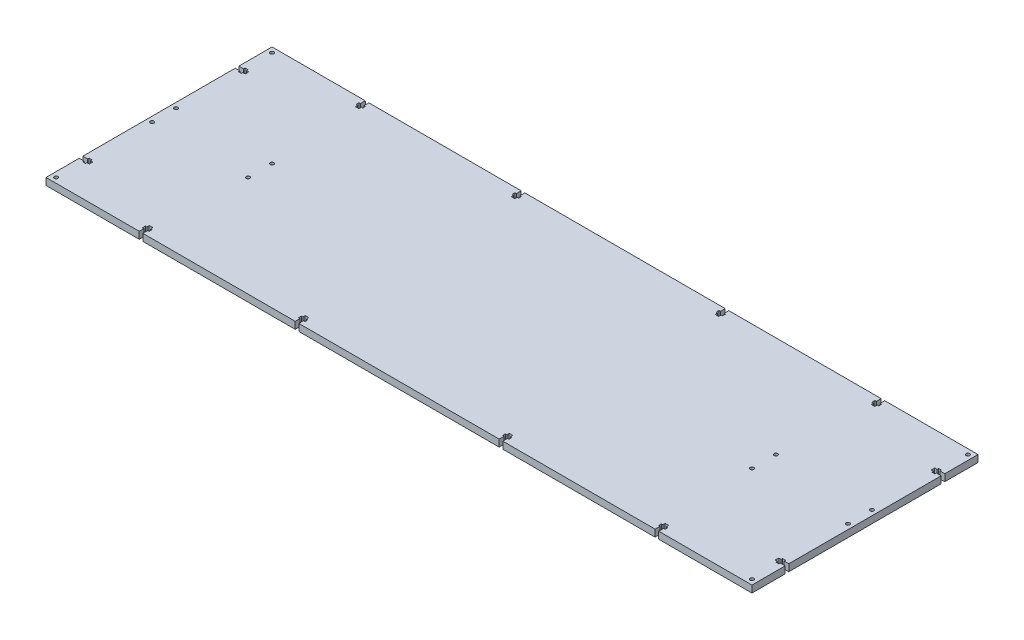
SolidWorks part; units mm, degrees
material "Acrylic (Medium-high impact)"
ref_plane "Front Plane" through (0, 0, 0) normal (0, 0, 1) x (1, 0, 0)
ref_plane "Top Plane" through (0, 0, 0) normal (0, 1, 0) x (1, 0, 0)
ref_plane "Right Plane" through (0, 0, 0) normal (1, 0, 0) x (0, 0, -1)
sketch "Sketch1" plane through (0, 0, 0) normal (0, 0, 1) x (1, 0, 0)
  line L1 (0, 0) -> (588.4, 0)
  line L2 (0, 0) -> (0, 5.8)
  line L3 (0, 5.8) -> (588.4, 5.8)
  line L4 (588.4, 0) -> (588.4, 5.8)
  line L5 (294.2, 5.8) -> (294.2, 0) construction
  line L6 (0, 2.9) -> (588.4, 2.9) construction
  point P80 (294.2, 2.9)
  dimension "D1" = 588.4
  dimension "D2" = 5.8
extrude "Boss-Extrude1" add sketch "Sketch1" along normal blind 188.4
sketch "Sketch2" plane through (0, 5.8, 0) normal (0, 1, 0) x (1, 0, 0)
  line L0 (294.2, 0) -> (294.2, -188.4) construction
  line L1 (588.4, 0) -> (0, 0) construction
  line L2 (588.4, -188.4) -> (0, -188.4) construction
  line L3 (94.2, -188.4) -> (94.2, 0) construction
  line L4 (494.2, -188.4) -> (494.2, 0) construction
  line L5 (30.7, -6.35) -> (31.91, -6.35)
  line L6 (27.7, -8.35) -> (30.7, -8.35)
  line L7 (30.7, -6.35) -> (30.7, -8.35)
  line L8 (27.7, -6.35) -> (27.7, -8.35)
  line L9 (26.49, -6.35) -> (27.7, -6.35)
  line L10 (31.91, -4) -> (31.91, -6.35)
  line L11 (26.49, -4) -> (27.7, -4)
  line L12 (26.49, -4) -> (26.49, -6.35)
  line L13 (30.7, -4) -> (31.91, -4)
  line L14 (30.7, 0) -> (30.7, -4)
  line L15 (27.7, 0) -> (30.7, 0)
  line L16 (27.7, 0) -> (27.7, -4)
  line L17 (160.7, 0) -> (160.7, -4)
  line L18 (160.7, 0) -> (157.7, 0)
  line L19 (157.7, 0) -> (157.7, -4)
  line L20 (157.7, -4) -> (156.49, -4)
  line L21 (161.91, -4) -> (161.91, -6.35)
  line L22 (161.91, -4) -> (160.7, -4)
  line L23 (156.49, -4) -> (156.49, -6.35)
  line L24 (161.91, -6.35) -> (160.7, -6.35)
  line L25 (160.7, -6.35) -> (160.7, -8.35)
  line L26 (157.7, -6.35) -> (157.7, -8.35)
  line L27 (160.7, -8.35) -> (157.7, -8.35)
  line L28 (157.7, -6.35) -> (156.49, -6.35)
  line L29 (94.2, -94.2) -> (294.2, -94.2) construction
  line L30 (194.2, -94.2) -> (194.2, 0) construction
  line L31 (230.7, -6.35) -> (231.91, -6.35)
  line L32 (227.7, -8.35) -> (230.7, -8.35)
  line L33 (230.7, -6.35) -> (230.7, -8.35)
  line L34 (227.7, -6.35) -> (227.7, -8.35)
  line L35 (226.49, -6.35) -> (227.7, -6.35)
  line L36 (231.91, -4) -> (231.91, -6.35)
  line L37 (226.49, -4) -> (227.7, -4)
  line L38 (226.49, -4) -> (226.49, -6.35)
  line L39 (230.7, -4) -> (231.91, -4)
  line L40 (230.7, 0) -> (230.7, -4)
  line L41 (227.7, 0) -> (230.7, 0)
  line L42 (227.7, 0) -> (227.7, -4)
  line L43 (360.7, 0) -> (360.7, -4)
  line L44 (360.7, 0) -> (357.7, 0)
  line L45 (357.7, 0) -> (357.7, -4)
  line L46 (357.7, -4) -> (356.49, -4)
  line L47 (361.91, -4) -> (361.91, -6.35)
  line L48 (361.91, -4) -> (360.7, -4)
  line L49 (356.49, -4) -> (356.49, -6.35)
  line L50 (361.91, -6.35) -> (360.7, -6.35)
  line L51 (360.7, -6.35) -> (360.7, -8.35)
  line L52 (357.7, -6.35) -> (357.7, -8.35)
  line L53 (360.7, -8.35) -> (357.7, -8.35)
  line L54 (357.7, -6.35) -> (356.49, -6.35)
  line L55 (294.2, -94.2) -> (494.2, -94.2) construction
  line L56 (394.2, -94.2) -> (394.2, 0) construction
  line L57 (430.7, -6.35) -> (431.91, -6.35)
  line L58 (427.7, -8.35) -> (430.7, -8.35)
  line L59 (430.7, -6.35) -> (430.7, -8.35)
  line L60 (427.7, -6.35) -> (427.7, -8.35)
  line L61 (426.49, -6.35) -> (427.7, -6.35)
  line L62 (431.91, -4) -> (431.91, -6.35)
  line L63 (426.49, -4) -> (427.7, -4)
  line L64 (426.49, -4) -> (426.49, -6.35)
  line L65 (430.7, -4) -> (431.91, -4)
  line L66 (430.7, 0) -> (430.7, -4)
  line L67 (427.7, 0) -> (430.7, 0)
  line L68 (427.7, 0) -> (427.7, -4)
  line L69 (560.7, 0) -> (560.7, -4)
  line L70 (560.7, 0) -> (557.7, 0)
  line L71 (557.7, 0) -> (557.7, -4)
  line L72 (557.7, -4) -> (556.49, -4)
  line L73 (561.91, -4) -> (561.91, -6.35)
  line L74 (561.91, -4) -> (560.7, -4)
  line L75 (556.49, -4) -> (556.49, -6.35)
  line L76 (561.91, -6.35) -> (560.7, -6.35)
  line L77 (560.7, -6.35) -> (560.7, -8.35)
  line L78 (557.7, -6.35) -> (557.7, -8.35)
  line L79 (560.7, -8.35) -> (557.7, -8.35)
  line L80 (557.7, -6.35) -> (556.49, -6.35)
  line L81 (557.7, -182.05) -> (556.49, -182.05)
  line L82 (560.7, -180.05) -> (557.7, -180.05)
  line L83 (557.7, -182.05) -> (557.7, -180.05)
  line L84 (560.7, -182.05) -> (560.7, -180.05)
  line L85 (561.91, -182.05) -> (560.7, -182.05)
  line L86 (556.49, -184.4) -> (556.49, -182.05)
  line L87 (561.91, -184.4) -> (560.7, -184.4)
  line L88 (561.91, -184.4) -> (561.91, -182.05)
  line L89 (557.7, -184.4) -> (556.49, -184.4)
  line L90 (557.7, -188.4) -> (557.7, -184.4)
  line L91 (560.7, -188.4) -> (557.7, -188.4)
  line L92 (560.7, -188.4) -> (560.7, -184.4)
  line L93 (427.7, -188.4) -> (427.7, -184.4)
  line L94 (427.7, -188.4) -> (430.7, -188.4)
  line L95 (430.7, -188.4) -> (430.7, -184.4)
  line L96 (430.7, -184.4) -> (431.91, -184.4)
  line L97 (426.49, -184.4) -> (426.49, -182.05)
  line L98 (426.49, -184.4) -> (427.7, -184.4)
  line L99 (431.91, -184.4) -> (431.91, -182.05)
  line L100 (426.49, -182.05) -> (427.7, -182.05)
  line L101 (427.7, -182.05) -> (427.7, -180.05)
  line L102 (430.7, -182.05) -> (430.7, -180.05)
  line L103 (427.7, -180.05) -> (430.7, -180.05)
  line L104 (430.7, -182.05) -> (431.91, -182.05)
  line L105 (357.7, -182.05) -> (356.49, -182.05)
  line L106 (360.7, -180.05) -> (357.7, -180.05)
  line L107 (357.7, -182.05) -> (357.7, -180.05)
  line L108 (360.7, -182.05) -> (360.7, -180.05)
  line L109 (361.91, -182.05) -> (360.7, -182.05)
  line L110 (356.49, -184.4) -> (356.49, -182.05)
  line L111 (361.91, -184.4) -> (360.7, -184.4)
  line L112 (361.91, -184.4) -> (361.91, -182.05)
  line L113 (357.7, -184.4) -> (356.49, -184.4)
  line L114 (357.7, -188.4) -> (357.7, -184.4)
  line L115 (360.7, -188.4) -> (357.7, -188.4)
  line L116 (360.7, -188.4) -> (360.7, -184.4)
  line L117 (227.7, -188.4) -> (227.7, -184.4)
  line L118 (227.7, -188.4) -> (230.7, -188.4)
  line L119 (230.7, -188.4) -> (230.7, -184.4)
  line L120 (230.7, -184.4) -> (231.91, -184.4)
  line L121 (226.49, -184.4) -> (226.49, -182.05)
  line L122 (226.49, -184.4) -> (227.7, -184.4)
  line L123 (231.91, -184.4) -> (231.91, -182.05)
  line L124 (226.49, -182.05) -> (227.7, -182.05)
  line L125 (227.7, -182.05) -> (227.7, -180.05)
  line L126 (230.7, -182.05) -> (230.7, -180.05)
  line L127 (227.7, -180.05) -> (230.7, -180.05)
  line L128 (230.7, -182.05) -> (231.91, -182.05)
  line L129 (157.7, -182.05) -> (156.49, -182.05)
  line L130 (160.7, -180.05) -> (157.7, -180.05)
  line L131 (157.7, -182.05) -> (157.7, -180.05)
  line L132 (160.7, -182.05) -> (160.7, -180.05)
  line L133 (161.91, -182.05) -> (160.7, -182.05)
  line L134 (156.49, -184.4) -> (156.49, -182.05)
  line L135 (161.91, -184.4) -> (160.7, -184.4)
  line L136 (161.91, -184.4) -> (161.91, -182.05)
  line L137 (157.7, -184.4) -> (156.49, -184.4)
  line L138 (157.7, -188.4) -> (157.7, -184.4)
  line L139 (160.7, -188.4) -> (157.7, -188.4)
  line L140 (160.7, -188.4) -> (160.7, -184.4)
  line L141 (27.7, -188.4) -> (27.7, -184.4)
  line L142 (27.7, -188.4) -> (30.7, -188.4)
  line L143 (30.7, -188.4) -> (30.7, -184.4)
  line L144 (30.7, -184.4) -> (31.91, -184.4)
  line L145 (26.49, -184.4) -> (26.49, -182.05)
  line L146 (26.49, -184.4) -> (27.7, -184.4)
  line L147 (31.91, -184.4) -> (31.91, -182.05)
  line L148 (26.49, -182.05) -> (27.7, -182.05)
  line L149 (27.7, -182.05) -> (27.7, -180.05)
  line L150 (30.7, -182.05) -> (30.7, -180.05)
  line L151 (27.7, -180.05) -> (30.7, -180.05)
  line L152 (30.7, -182.05) -> (31.91, -182.05)
  line L153 (94.2, -94.2) -> (0, -94.2) construction
  line L154 (0, -188.4) -> (0, 0) construction
  line L155 (6.35, -27.7) -> (6.35, -26.49)
  line L156 (8.35, -30.7) -> (8.35, -27.7)
  line L157 (6.35, -27.7) -> (8.35, -27.7)
  line L158 (6.35, -30.7) -> (8.35, -30.7)
  line L159 (6.35, -31.91) -> (6.35, -30.7)
  line L160 (4, -26.49) -> (6.35, -26.49)
  line L161 (4, -31.91) -> (4, -30.7)
  line L162 (4, -31.91) -> (6.35, -31.91)
  line L163 (4, -27.7) -> (4, -26.49)
  line L164 (0, -27.7) -> (4, -27.7)
  line L165 (0, -30.7) -> (0, -27.7)
  line L166 (0, -30.7) -> (4, -30.7)
  line L167 (0, -157.7) -> (4, -157.7)
  line L168 (0, -157.7) -> (0, -160.7)
  line L169 (0, -160.7) -> (4, -160.7)
  line L170 (4, -160.7) -> (4, -161.91)
  line L171 (4, -156.49) -> (6.35, -156.49)
  line L172 (4, -156.49) -> (4, -157.7)
  line L173 (4, -161.91) -> (6.35, -161.91)
  line L174 (6.35, -156.49) -> (6.35, -157.7)
  line L175 (6.35, -157.7) -> (8.35, -157.7)
  line L176 (6.35, -160.7) -> (8.35, -160.7)
  line L177 (8.35, -157.7) -> (8.35, -160.7)
  line L178 (6.35, -160.7) -> (6.35, -161.91)
  line L179 (582.05, -160.7) -> (582.05, -161.91)
  line L180 (580.05, -157.7) -> (580.05, -160.7)
  line L181 (582.05, -160.7) -> (580.05, -160.7)
  line L182 (582.05, -157.7) -> (580.05, -157.7)
  line L183 (582.05, -156.49) -> (582.05, -157.7)
  line L184 (584.4, -161.91) -> (582.05, -161.91)
  line L185 (584.4, -156.49) -> (584.4, -157.7)
  line L186 (584.4, -156.49) -> (582.05, -156.49)
  line L187 (584.4, -160.7) -> (584.4, -161.91)
  line L188 (588.4, -160.7) -> (584.4, -160.7)
  line L189 (588.4, -157.7) -> (588.4, -160.7)
  line L190 (588.4, -157.7) -> (584.4, -157.7)
  line L191 (588.4, -30.7) -> (584.4, -30.7)
  line L192 (588.4, -30.7) -> (588.4, -27.7)
  line L193 (588.4, -27.7) -> (584.4, -27.7)
  line L194 (584.4, -27.7) -> (584.4, -26.49)
  line L195 (584.4, -31.91) -> (582.05, -31.91)
  line L196 (584.4, -31.91) -> (584.4, -30.7)
  line L197 (584.4, -26.49) -> (582.05, -26.49)
  line L198 (582.05, -31.91) -> (582.05, -30.7)
  line L199 (582.05, -30.7) -> (580.05, -30.7)
  line L200 (582.05, -27.7) -> (580.05, -27.7)
  line L201 (580.05, -30.7) -> (580.05, -27.7)
  line L202 (582.05, -27.7) -> (582.05, -26.49)
  point P22 (29.2, -8.35)
  point P177 (8.35, -29.2)
  dimension "D1" = 200
  dimension "D2" = 200
  dimension "D3" = 3
  dimension "D4" = 4
  dimension "D5" = 2.35
  dimension "D6" = 5.42
  dimension "D7" = 2
  dimension "D8" = 65
  dimension "D9" = 3
  dimension "D10" = 4
  dimension "D11" = 2.35
  dimension "D12" = 5.42
  dimension "D13" = 2
  dimension "D14" = 65
extrude "Cut-Extrude1" cut sketch "Sketch2" against normal up to surface (5.8 mm away) contours L152 L150 L151 L149 L148 L145 L146 L141 L143 L144 L147 | L140 L135 L136 L133 L132 L130 L131 L129 L134 L137 L138 | L128 L126 L127 L125 L124 L121 L122 L117 L119 L120 L123 | L116 L111 L112 L109 L108 L106 L107 L105 L110 L113 L114 | L104 L102 L103 L101 L100 L97 L98 L93 L95 L96 L99 | L92 L87 L88 L85 L84 L82 L83 L81 L86 L89 L90 | L80 L78 L79 L77 L76 L73 L74 L69 L71 L72 L75 | L68 L63 L64 L61 L60 L58 L59 L57 L62 L65 L66 | L54 L52 L53 L51 L50 L47 L48 L43 L45 L46 L49 | L42 L37 L38 L35 L34 L32 L33 L31 L36 L39 L40 | L28 L26 L27 L25 L24 L21 L22 L17 L19 L20 L23 | L16 L11 L12 L9 L8 L6 L7 L5 L10 L13 L14 region at (29.2, 5.8, 4.36) region at (159.2, 5.8, 4.36) region at (229.2, 5.8, 4.36) region at (359.2, 5.8, 4.36) region at (429.2, 5.8, 4.36) region at (559.2, 5.8, 4.36) region at (559.2, 5.8, 184.04) region at (429.2, 5.8, 184.04) region at (359.2, 5.8, 184.04) region at (229.2, 5.8, 184.04) region at (159.2, 5.8, 184.04) region at (29.2, 5.8, 184.04) up to face at (294.2, 0, 94.2)
extrude "Cut-Extrude2" cut sketch "Sketch2<3>" against normal up to surface (5.8 mm away) contours L178 L176 L177 L175 L174 L171 L172 L167 L169 L170 L173 | L166 L161 L162 L159 L158 L156 L157 L155 L160 L163 L164 | L190 L185 L186 L183 L182 L180 L181 L179 L184 L187 L188 | L202 L200 L201 L199 L198 L195 L196 L191 L193 L194 L197 region at (4.36, 5.8, 29.2) region at (4.36, 5.8, 159.2) region at (584.04, 5.8, 159.2) region at (584.04, 5.8, 29.2) up to face at (294.2, 0, 94.2)
sketch "Sketch2<3>" plane through (0, 5.8, 0) normal (0, 1, 0) x (1, 0, 0) same geometry as "Sketch2"
sketch "Sketch4" [suppressed] plane through (0, 0, 0) normal (0, -1, 0) x (1, 0, 0)
  line L0 (588.4, 188.4) -> (588.4, 0) construction
  line L1 (394.2, 151.459) -> (405.2, 151.459)
  line L2 (394.2, 151.459) -> (394.2, 139.459)
  line L3 (394.2, 139.459) -> (405.2, 139.459)
  line L4 (407.2, 149.459) -> (407.2, 141.459)
  line L5 (399.7, 139.459) -> (399.7, 151.459) construction
  line L6 (394.2, 145.459) -> (407.2, 145.459) construction
  line L7 (194.2, 151.459) -> (205.2, 151.459)
  line L12 (360.7, 188.4) -> (427.7, 188.4) construction
  line L13 (394.2, 138.959) -> (405.2, 138.959)
  line L14 (407.7, 149.459) -> (407.7, 141.459)
  line L15 (394.2, 151.959) -> (405.2, 151.959)
  line L17 (194.2, 151.459) -> (194.2, 139.459)
  line L18 (194.2, 139.459) -> (205.2, 139.459)
  line L19 (207.2, 149.459) -> (207.2, 141.459)
  line L20 (194.2, 138.959) -> (205.2, 138.959)
  line L21 (207.7, 149.459) -> (207.7, 141.459)
  line L22 (194.2, 151.959) -> (205.2, 151.959)
  line L24 (199.7, 139.459) -> (199.7, 151.459) construction
  line L25 (194.2, 145.459) -> (207.2, 145.459) construction
  line L26 (394.2, 151.459) -> (394.2, 151.959)
  line L27 (394.2, 139.459) -> (394.2, 138.959)
  line L28 (194.2, 151.459) -> (194.2, 151.959)
  line L29 (194.2, 139.459) -> (194.2, 138.959)
  line L30 (393.7, 151.959) -> (405.2, 151.959) construction
  line L32 (393.7, 151.959) -> (393.7, 138.959) construction
  line L33 (393.7, 138.959) -> (405.2, 138.959) construction
  arc A0 (405.2, 139.459) -> (407.2, 141.459) centre (405.2, 141.459) ccw
  arc A1 (405.2, 151.459) -> (407.2, 149.459) centre (405.2, 149.459) cw
  arc A2 (405.2, 138.959) -> (407.7, 141.459) centre (405.2, 141.459) ccw
  arc A3 (405.2, 151.959) -> (407.7, 149.459) centre (405.2, 149.459) cw
  arc A4 (205.2, 139.459) -> (207.2, 141.459) centre (205.2, 141.459) ccw
  arc A5 (205.2, 151.459) -> (207.2, 149.459) centre (205.2, 149.459) cw
  arc A6 (205.2, 138.959) -> (207.7, 141.459) centre (205.2, 141.459) ccw
  arc A7 (205.2, 151.959) -> (207.7, 149.459) centre (205.2, 149.459) cw
  point P16 (407.2, 151.459)
  point P42 (199.7, 145.459)
  point P72 (399.7, 145.459)
  dimension "D6" = 2
  dimension "D1" = 181.2
  dimension "D2" = 36.941
  dimension "D3" = 13
  dimension "D4" = 12
  dimension "D7" = 0.5
extrude "Cut-Extrude3" [suppressed] cut sketch "Sketch4" against normal blind 10
sketch "Sketch5" plane through (0, 0, 0) normal (0, -1, 0) x (1, 0, 0)
  line L0 (588.4, 188.4) -> (588.4, 160.7) construction
  line L1 (0, 188.4) -> (588.4, 188.4)
  line L2 (0, 188.4) -> (0, 178.1911)
  line L3 (0, 178.1911) -> (588.4, 178.1911)
  line L4 (588.4, 188.4) -> (588.4, 178.1911)
  line L5 (294.2, 178.1911) -> (294.2, 188.4) construction
  line L6 (0, 183.2956) -> (588.4, 183.2956) construction
  line L7 (0, 27.7) -> (0, 0) construction
  line L8 (588.4, 0) -> (0, 0)
  line L9 (588.4, 0) -> (588.4, 13.85)
  line L10 (588.4, 13.85) -> (0, 13.85)
  line L11 (0, 0) -> (0, 13.85)
  line L12 (294.2, 13.85) -> (294.2, 0) construction
  line L13 (588.4, 6.925) -> (0, 6.925) construction
  point P218 (294.2, 6.925)
  point P232 (294.2, 183.2956)
extrude "Boss-Extrude2" add sketch "Sketch5" against normal up to surface (5.8 mm away) up to face at (294.2, 5.8, 94.2)
sketch "Sketch6" plane through (0, 0, 0) normal (0, -1, 0) x (1, 0, 0)
  line L0 (8.35, 160.7) -> (8.35, 157.7) construction
  line L1 (0, 188.4) -> (588.4, 188.4) construction
  line L2 (0, 188.4) -> (0, 0) construction
  line L3 (0, 0) -> (588.4, 0) construction
  line L4 (588.4, 188.4) -> (588.4, 0) construction
  line L5 (294.2, 0) -> (294.2, 188.4) construction
  line L6 (0, 94.2) -> (588.4, 94.2) construction
  line L7 (6.35, 157.7) -> (6.35, 156.49) construction
  line L8 (6.35, 161.91) -> (6.35, 160.7) construction
  line L9 (4, 161.91) -> (4, 160.7) construction
  line L10 (6.35, 161.91) -> (4, 161.91) construction
  line L11 (4, 157.7) -> (4, 156.49) construction
  line L12 (4, 157.7) -> (0, 157.7) construction
  line L13 (4, 160.7) -> (0, 160.7) construction
  line L14 (8.35, 160.7) -> (6.35, 160.7) construction
  line L15 (8.35, 157.7) -> (6.35, 157.7) construction
  line L16 (6.35, 156.49) -> (4, 156.49) construction
  line L17 (8.35, 160.7) -> (8.35, 157.7)
  line L18 (6.35, 157.7) -> (6.35, 156.49)
  line L19 (6.35, 161.91) -> (6.35, 160.7)
  line L20 (4, 161.91) -> (4, 160.7)
  line L21 (6.35, 161.91) -> (4, 161.91)
  line L22 (4, 157.7) -> (4, 156.49)
  line L23 (4, 157.7) -> (0, 157.7)
  line L24 (4, 160.7) -> (0, 160.7)
  line L25 (8.35, 160.7) -> (6.35, 160.7)
  line L26 (8.35, 157.7) -> (6.35, 157.7)
  line L27 (6.35, 156.49) -> (4, 156.49)
  line L28 (77.7, 182.05) -> (76.49, 182.05)
  line L29 (76.49, 182.05) -> (76.49, 184.4)
  line L30 (80.7, 184.4) -> (80.7, 188.4)
  line L31 (81.91, 182.05) -> (80.7, 182.05)
  line L32 (77.7, 184.4) -> (76.49, 184.4)
  line L33 (77.7, 180.05) -> (77.7, 182.05)
  line L34 (80.7, 180.05) -> (77.7, 180.05)
  line L35 (81.91, 182.05) -> (81.91, 184.4)
  line L36 (80.7, 180.05) -> (80.7, 182.05)
  line L37 (81.91, 184.4) -> (80.7, 184.4)
  line L38 (77.7, 184.4) -> (77.7, 188.4)
  line L39 (0, 66.425) -> (294.2, 66.425) construction
  line L40 (144.2, 66.425) -> (144.2, 188.4) construction
  line L41 (210.7, 188.4) -> (207.7, 188.4)
  line L42 (210.7, 184.4) -> (210.7, 188.4)
  line L43 (206.49, 184.4) -> (207.7, 184.4)
  line L44 (207.7, 180.05) -> (207.7, 182.05)
  line L45 (206.49, 182.05) -> (206.49, 184.4)
  line L46 (207.7, 180.05) -> (210.7, 180.05)
  line L47 (210.7, 180.05) -> (210.7, 182.05)
  line L48 (210.7, 184.4) -> (211.91, 184.4)
  line L49 (206.49, 182.05) -> (207.7, 182.05)
  line L50 (77.7, 188.4) -> (80.7, 188.4)
  line L52 (207.7, 184.4) -> (207.7, 188.4)
  line L53 (211.91, 182.05) -> (211.91, 184.4)
  line L54 (210.7, 182.05) -> (211.91, 182.05)
  line L55 (377.7, 182.05) -> (376.49, 182.05)
  line L56 (376.49, 182.05) -> (376.49, 184.4)
  line L57 (380.7, 184.4) -> (380.7, 188.4)
  line L58 (510.7, 188.4) -> (507.7, 188.4)
  line L59 (381.91, 182.05) -> (380.7, 182.05)
  line L60 (377.7, 184.4) -> (376.49, 184.4)
  line L61 (377.7, 180.05) -> (377.7, 182.05)
  line L62 (380.7, 180.05) -> (377.7, 180.05)
  line L63 (381.91, 182.05) -> (381.91, 184.4)
  line L64 (380.7, 180.05) -> (380.7, 182.05)
  line L65 (381.91, 184.4) -> (380.7, 184.4)
  line L66 (377.7, 184.4) -> (377.7, 188.4)
  line L67 (377.7, 188.4) -> (380.7, 188.4)
  line L68 (510.7, 184.4) -> (510.7, 188.4)
  line L69 (506.49, 184.4) -> (507.7, 184.4)
  line L70 (507.7, 180.05) -> (507.7, 182.05)
  line L71 (506.49, 182.05) -> (506.49, 184.4)
  line L72 (507.7, 180.05) -> (510.7, 180.05)
  line L73 (510.7, 180.05) -> (510.7, 182.05)
  line L74 (510.7, 184.4) -> (511.91, 184.4)
  line L75 (506.49, 182.05) -> (507.7, 182.05)
  line L76 (507.7, 184.4) -> (507.7, 188.4)
  line L77 (511.91, 182.05) -> (511.91, 184.4)
  line L78 (510.7, 182.05) -> (511.91, 182.05)
  line L79 (510.7, 6.35) -> (511.91, 6.35)
  line L80 (511.91, 6.35) -> (511.91, 4)
  line L81 (507.7, 4) -> (507.7, 0)
  line L82 (506.49, 6.35) -> (507.7, 6.35)
  line L83 (510.7, 4) -> (511.91, 4)
  line L84 (510.7, 8.35) -> (510.7, 6.35)
  line L85 (507.7, 8.35) -> (510.7, 8.35)
  line L86 (506.49, 6.35) -> (506.49, 4)
  line L87 (507.7, 8.35) -> (507.7, 6.35)
  line L88 (506.49, 4) -> (507.7, 4)
  line L89 (510.7, 4) -> (510.7, 0)
  line L90 (377.7, 0) -> (380.7, 0)
  line L91 (377.7, 4) -> (377.7, 0)
  line L92 (381.91, 4) -> (380.7, 4)
  line L93 (380.7, 8.35) -> (380.7, 6.35)
  line L94 (381.91, 6.35) -> (381.91, 4)
  line L95 (380.7, 8.35) -> (377.7, 8.35)
  line L96 (377.7, 8.35) -> (377.7, 6.35)
  line L97 (377.7, 4) -> (376.49, 4)
  line L98 (381.91, 6.35) -> (380.7, 6.35)
  line L99 (510.7, 0) -> (507.7, 0)
  line L100 (380.7, 4) -> (380.7, 0)
  line L101 (376.49, 6.35) -> (376.49, 4)
  line L102 (377.7, 6.35) -> (376.49, 6.35)
  line L103 (210.7, 6.35) -> (211.91, 6.35)
  line L104 (211.91, 6.35) -> (211.91, 4)
  line L105 (207.7, 4) -> (207.7, 0)
  line L106 (77.7, 0) -> (80.7, 0)
  line L107 (206.49, 6.35) -> (207.7, 6.35)
  line L108 (210.7, 4) -> (211.91, 4)
  line L109 (210.7, 8.35) -> (210.7, 6.35)
  line L110 (207.7, 8.35) -> (210.7, 8.35)
  line L111 (206.49, 6.35) -> (206.49, 4)
  line L112 (207.7, 8.35) -> (207.7, 6.35)
  line L113 (206.49, 4) -> (207.7, 4)
  line L114 (210.7, 4) -> (210.7, 0)
  line L115 (210.7, 0) -> (207.7, 0)
  line L116 (77.7, 4) -> (77.7, 0)
  line L117 (81.91, 4) -> (80.7, 4)
  line L118 (80.7, 8.35) -> (80.7, 6.35)
  line L119 (81.91, 6.35) -> (81.91, 4)
  line L120 (80.7, 8.35) -> (77.7, 8.35)
  line L121 (77.7, 8.35) -> (77.7, 6.35)
  line L122 (77.7, 4) -> (76.49, 4)
  line L123 (81.91, 6.35) -> (80.7, 6.35)
  line L124 (80.7, 4) -> (80.7, 0)
  line L125 (76.49, 6.35) -> (76.49, 4)
  line L126 (77.7, 6.35) -> (76.49, 6.35)
  point P44 (79.2, 180.05)
  point P45 (209.2, 180.05)
  point P224 (294.2, 94.2)
  dimension "D1" = 3
  dimension "D2" = 4
  dimension "D3" = 2.35
  dimension "D4" = 2
  dimension "D5" = 1.21
  dimension "D6" = 130
  dimension "D7" = 79.2
extrude "Cut-Extrude4" cut sketch "Sketch6" against normal up to surface (5.8 mm away) contours L50 L38 L32 L29 L28 L33 L34 L36 L31 L35 L37 L30 | L47 L54 L53 L48 L42 L41 L52 L43 L45 L49 L44 L46 | L67 L66 L60 L56 L55 L61 L62 L64 L59 L63 L65 L57 | L73 L78 L77 L74 L68 L58 L76 L69 L71 L75 L70 L72 | L99 L89 L83 L80 L79 L84 L85 L87 L82 L86 L88 L81 | L96 L102 L101 L97 L91 L90 L100 L92 L94 L98 L93 L95 | L115 L114 L108 L104 L103 L109 L110 L112 L107 L111 L113 L105 | L121 L126 L125 L122 L116 L106 L124 L117 L119 L123 L118 L120 region at (79.2, 0, 184.04) region at (209.2, 0, 184.04) region at (379.2, 0, 184.04) region at (509.2, 0, 184.04) region at (509.2, 0, 4.36) region at (379.2, 0, 4.36) region at (209.2, 0, 4.36) region at (79.2, 0, 4.36) up to face at (294.2, 5.8, 94.2)
sketch "Sketch7" [suppressed] plane through (0, 5.8, 0) normal (0, 1, 0) x (1, 0, 0)
  line L0 (357.7, -188.4) -> (230.7, -188.4) construction
  line L1 (254.2, -168.4) -> (334.2, -168.4)
  line L2 (244.2, -158.4) -> (244.2, -78.4)
  line L3 (254.2, -68.4) -> (334.2, -68.4)
  line L4 (344.2, -158.4) -> (344.2, -78.4)
  line L5 (244.2, -168.4) -> (344.2, -68.4) construction
  line L6 (244.2, -68.4) -> (344.2, -168.4) construction
  line L9 (378.45, -145.459) -> (378.45, -139.459) construction
  line L10 (371.7, -145.459) -> (378.45, -145.459) construction
  line L11 (385.2, -145.459) -> (371.7, -145.459) construction
  line L12 (385.2, -139.459) -> (385.2, -138.959)
  line L13 (385.2, -138.959) -> (374.2, -138.959)
  line L14 (371.7, -149.459) -> (371.7, -141.459)
  line L15 (385.2, -151.959) -> (374.2, -151.959)
  line L16 (385.2, -151.459) -> (385.2, -151.959)
  line L17 (385.2, -139.459) -> (374.2, -139.459)
  line L18 (372.2, -149.459) -> (372.2, -141.459)
  line L19 (385.2, -151.459) -> (374.2, -151.459)
  line L20 (385.2, -151.459) -> (385.2, -139.459)
  arc A0 (371.7, -141.459) -> (374.2, -138.959) centre (374.2, -141.459) cw
  arc A1 (374.2, -151.959) -> (371.7, -149.459) centre (374.2, -149.459) cw
  arc A2 (372.2, -141.459) -> (374.2, -139.459) centre (374.2, -141.459) cw
  arc A3 (374.2, -151.459) -> (372.2, -149.459) centre (374.2, -149.459) cw
  arc A16 (334.2, -168.4) -> (344.2, -158.4) centre (334.2, -158.4) ccw
  arc A17 (254.2, -168.4) -> (244.2, -158.4) centre (254.2, -158.4) cw
  arc A18 (334.2, -68.4) -> (344.2, -78.4) centre (334.2, -78.4) cw
  arc A19 (244.2, -78.4) -> (254.2, -68.4) centre (254.2, -78.4) cw
  point P0 (294.2, -118.4)
  point P8 (294.2, -188.4)
  dimension "D3" = 10
  dimension "D1" = 100
  dimension "D2" = 20
extrude "Cut-Extrude5" [suppressed] cut sketch "Sketch7" against normal up to surface (5.8 mm away) contours L19 A3 L18 A2 L17 L12 L13 A0 L14 A1 L15 L16 | A3 L19 L20 L17 A2 L18 | A19 L2 A17 L1 A16 L4 A18 L3
sketch "Sketch8" plane through (0, 5.8, 0) normal (0, 1, 0) x (1, 0, 0)
  line L0 (0, -157.7) -> (0, -30.7) construction
  line L1 (4.2, -4.2) -> (84.2, -4.2) construction
  line L2 (4.2, -4.2) -> (4.2, -84.2) construction
  line L3 (4.2, -84.2) -> (84.2, -84.2) construction
  line L4 (84.2, -4.2) -> (84.2, -84.2) construction
  line L5 (44.2, -84.2) -> (44.2, -4.2) construction
  line L6 (4.2, -44.2) -> (84.2, -44.2) construction
  line L7 (77.7, 0) -> (0, 0) construction
  line L8 (0, -94.2) -> (116.4452, -94.2) construction
  line L9 (4.2, -144.2) -> (84.2, -144.2) construction
  line L10 (44.2, -104.2) -> (44.2, -184.2) construction
  line L11 (84.2, -184.2) -> (84.2, -104.2) construction
  line L12 (4.2, -104.2) -> (84.2, -104.2) construction
  line L13 (4.2, -184.2) -> (4.2, -104.2) construction
  line L14 (4.2, -184.2) -> (84.2, -184.2) construction
  line L15 (294.2, 0) -> (294.2, -188.4) construction
  line L16 (377.7, 0) -> (210.7, 0) construction
  line L17 (377.7, -188.4) -> (210.7, -188.4) construction
  line L18 (584.2, -184.2) -> (504.2, -184.2) construction
  line L19 (584.2, -184.2) -> (584.2, -104.2) construction
  line L20 (584.2, -104.2) -> (504.2, -104.2) construction
  line L21 (504.2, -184.2) -> (504.2, -104.2) construction
  line L22 (544.2, -104.2) -> (544.2, -184.2) construction
  line L23 (584.2, -144.2) -> (504.2, -144.2) construction
  line L24 (588.4, -94.2) -> (471.9548, -94.2) construction
  line L25 (584.2, -44.2) -> (504.2, -44.2) construction
  line L26 (544.2, -84.2) -> (544.2, -4.2) construction
  line L27 (504.2, -4.2) -> (504.2, -84.2) construction
  line L28 (584.2, -84.2) -> (504.2, -84.2) construction
  line L29 (584.2, -4.2) -> (584.2, -84.2) construction
  line L30 (584.2, -4.2) -> (504.2, -4.2) construction
  circle A0 centre (4.2, -4.2) radius 1.5
  circle A1 centre (4.2, -84.2) radius 1.5
  circle A2 centre (84.2, -84.2) radius 1.5
  circle A3 centre (84.2, -104.2) radius 1.5
  circle A4 centre (4.2, -104.2) radius 1.5
  circle A5 centre (4.2, -184.2) radius 1.5
  circle A6 centre (584.2, -184.2) radius 1.5
  circle A7 centre (584.2, -104.2) radius 1.5
  circle A8 centre (504.2, -104.2) radius 1.5
  circle A9 centre (504.2, -84.2) radius 1.5
  circle A10 centre (584.2, -84.2) radius 1.5
  circle A11 centre (584.2, -4.2) radius 1.5
  point P18 (44.2, -144.2)
  point P55 (544.2, -44.2)
  point P56 (544.2, -144.2)
  point P268 (44.2, -44.2)
  dimension "D4" = 3
  dimension "D1" = 4.2
  dimension "D2" = 4.2
  dimension "D3" = 80
extrude "Cut-Extrude6" cut sketch "Sketch8" against normal up to surface (5.8 mm away) up to face at (294.2, 0, 94.2)
sketch "Sketch9" [suppressed] plane through (0, 5.8, 0) normal (0, 1, 0) x (1, 0, 0)
  line L0 (194.2, -151.959) -> (194.2, -138.959) construction
  line L1 (194.2, -138.959) -> (205.2, -138.959) construction
  line L2 (207.7, -149.459) -> (207.7, -141.459) construction
  line L3 (194.2, -151.959) -> (205.2, -151.959) construction
  line L4 (194.2, -151.959) -> (194.2, -138.959)
  line L5 (194.2, -138.959) -> (205.2, -138.959)
  line L6 (207.7, -149.459) -> (207.7, -141.459)
  line L7 (194.2, -151.959) -> (205.2, -151.959)
  arc A0 (207.7, -141.459) -> (205.2, -138.959) centre (205.2, -141.459) ccw construction
  arc A1 (205.2, -151.959) -> (207.7, -149.459) centre (205.2, -149.459) ccw construction
  arc A2 (207.7, -141.459) -> (205.2, -138.959) centre (205.2, -141.459) ccw
  arc A3 (205.2, -151.959) -> (207.7, -149.459) centre (205.2, -149.459) ccw
extrude "Boss-Extrude3" [suppressed] add sketch "Sketch9" against normal up to surface (5.8 mm away)
